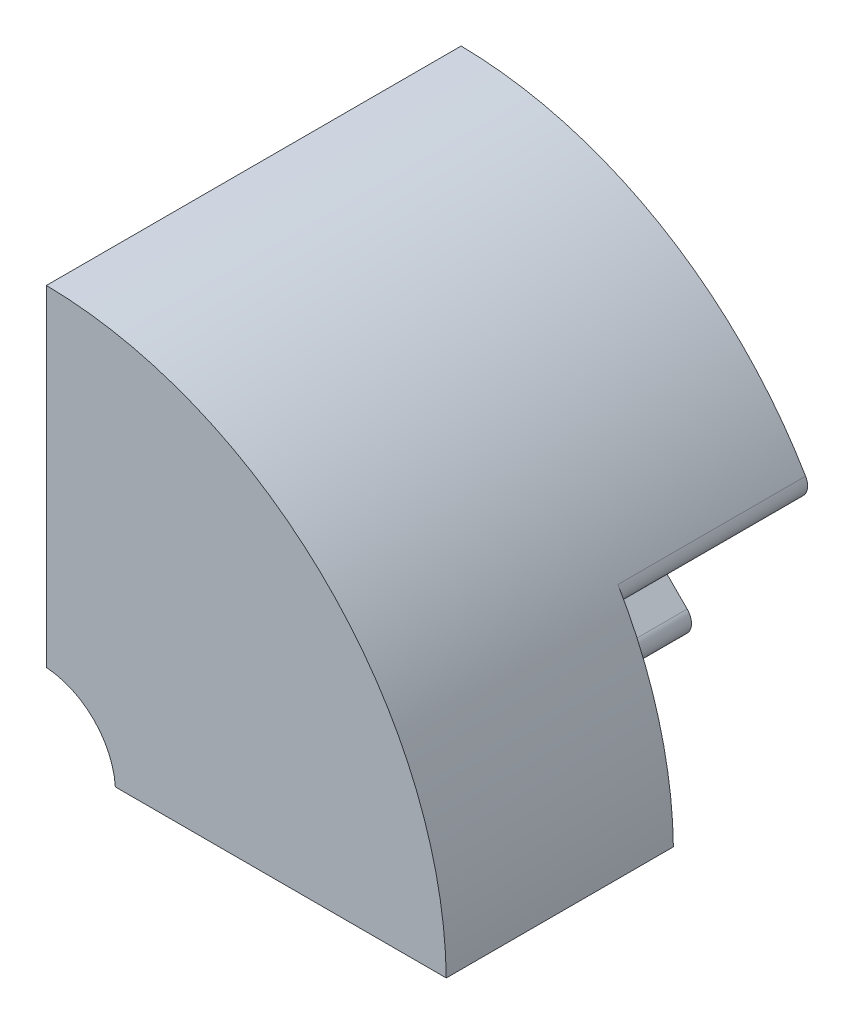
SolidWorks part; units mm, degrees
ref_plane "Front Plane" through (0, 0, 0) normal (0, 0, 1) x (1, 0, 0)
ref_plane "Top Plane" through (0, 0, 0) normal (0, 1, 0) x (1, 0, 0)
ref_plane "Right Plane" through (0, 0, 0) normal (1, 0, 0) x (0, 0, -1)
sketch "Sketch1" plane through (0, 0, 0) normal (0, 0, 1) x (1, 0, 0)
  line L0 (0.5, 40.997) -> (0.5, 7.4833)
  line L1 (7.4833, 0.5) -> (40.997, 0.5)
  arc A0 (7.4833, 0.5) -> (0.5, 7.4833) centre (0, 0) ccw
  arc A1 (40.997, 0.5) -> (0.5, 40.997) centre (0, 0) ccw
  dimension "D1" = 41
extrude "Boss-Extrude1" add sketch "Sketch1" against normal blind 42
sketch "Sketch2" plane through (0, 0, -42) normal (0, 0, -1) x (-1, 0, 0)
  line L0 (-38.6838, 7.5711) -> (-6.864, 39.3909)
  line L1 (-38.6838, 7.5711) -> (-34.4411, 3.3284)
  line L2 (-6.864, 39.3909) -> (-2.6213, 35.1482)
  line L3 (-34.4411, 3.3284) -> (-2.6213, 35.1482)
  line L4 (-34.0876, 17.8241) -> (-14.2886, 37.6231)
  line L5 (-34.0876, 17.8241) -> (-31.2591, 14.9957)
  line L6 (-14.2886, 37.6231) -> (-11.4602, 34.7947)
  line L7 (-31.2591, 14.9957) -> (-11.4602, 34.7947)
  line L8 (-31.6127, 6.1569) -> (-6.1569, 31.6127)
  line L9 (-31.6127, 6.1569) -> (-25.9558, 0.5)
  line L10 (-6.1569, 31.6127) -> (-0.5, 25.9558)
  line L11 (-25.9558, 0.5) -> (-0.5, 25.9558)
  line L12 (-7.4833, 0.5) -> (-40.997, 0.5) construction
  line L13 (-0.5, 40.997) -> (-0.5, 7.4833) construction
  line L14 (-25.9558, 0.5) -> (-7.4833, 0.5) construction
  line L15 (-7.4833, 0.5) -> (-0.5, 7.4833) construction
  line L16 (-0.5, 7.4833) -> (-0.5, 25.9558) construction
  point P0 (0, 0)
  dimension "D1" = 45
  dimension "D2" = 6
  dimension "D3" = 4
  dimension "D4" = 28
  dimension "D5" = 8
  dimension "D6" = 36
  dimension "D7" = 5
  dimension "D8" = 6.5
extrude "Cut-Extrude2" cut sketch "Sketch2" against normal blind 19 contours L1 L3 L2 L0 | L6 L4 L5 L0 region at (20.6525, 21.3597, -42) region at (22.7739, 26.3094, -42)
sketch "Sketch3" plane through (0, 0, -42) normal (0, 0, -1) x (-1, 0, 0)
  line L0 (-34.0876, 17.8241) -> (-35.9593, 19.6959)
  line L1 (-25.9558, 0.5) -> (-40.997, 0.5)
  line L4 (-6.2276, 31.542) -> (-0.5707, 25.8851)
  line L5 (-25.9558, 0.5) -> (-0.5707, 25.8851)
  line L6 (-34.4411, 3.3284) -> (-2.6213, 35.1482) construction
  line L7 (-6.2276, 31.542) -> (-34.0876, 17.8241)
  line L8 (-34.0876, 17.8241) -> (-31.2591, 14.9957) construction
  arc A0 (-0.5, 40.997) -> (-40.997, 0.5) centre (0, 0) ccw construction
  arc A1 (-35.9593, 19.6959) -> (-40.997, 0.5) centre (0, 0) ccw
  dimension "D1" = 8
  dimension "D2" = 35.9
extrude "Cut-Extrude3" cut sketch "Sketch3" against normal up to surface (19 mm away) up to face at (21.7132, 23.8345, -23)
sketch "Sketch4" plane through (0, 0, -23) normal (0, 0, -1) x (-1, 0, 0)
  line L0 (-14.2886, 37.6231) -> (-34.0876, 17.8241)
  line L1 (-14.2886, 37.6231) -> (-11.4602, 34.7947)
  line L2 (-34.0876, 17.8241) -> (-31.2591, 14.9957)
  line L3 (-11.4602, 34.7947) -> (-31.2591, 14.9957)
  line L7 (-11.4602, 34.7947) -> (-6.864, 39.3909) construction
extrude "Cut-Extrude4" cut sketch "Sketch4" against normal blind 22
sketch "Sketch5" plane through (0, 0, -42) normal (0, 0, -1) x (-1, 0, 0)
  line L0 (-18.8848, 0.5) -> (-0.5, 18.8848)
  line L1 (-7.4833, 0.5) -> (-25.9558, 0.5) construction
  line L2 (-0.5, 40.997) -> (-0.5, 7.4833) construction
  line L3 (-0.5, 18.8848) -> (-0.5, 0.5)
  line L4 (-0.5, 0.5) -> (-18.8848, 0.5)
  line L5 (-0.5707, 25.8851) -> (-25.9558, 0.5) construction
  dimension "D1" = 5
extrude "Cut-Extrude5" cut sketch "Sketch5" against normal blind 15
fillet "Fillet1" radius 1.5 7 edges at (11.4602, 34.7947, -32.5) (6.2276, 31.542, -32.5) (25.9558, 0.5, -32.5) (35.9593, 19.6959, -32.5) (34.0876, 17.8241, -32.5) (0.5, 18.8848, -34.5) (18.8848, 0.5, -34.5)
fillet "Fillet2" radius 3 3 edges at (0.6142, 18.9321, -27) (18.9321, 0.6142, -27) (9.6924, 9.6924, -27)
